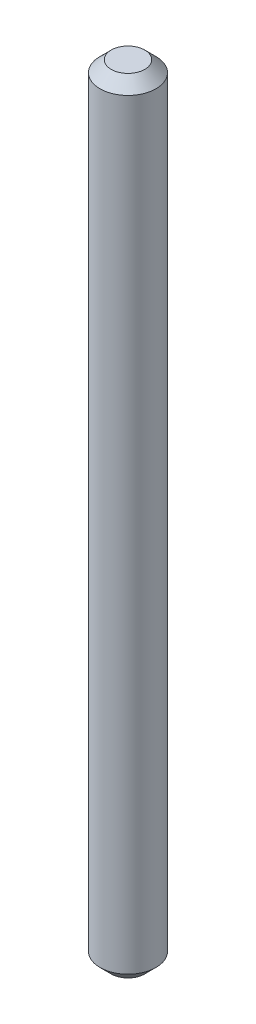
SolidWorks part; units mm, degrees
ref_plane "Plan de face" through (0, 0, 0) normal (0, 0, 1) x (1, 0, 0)
ref_plane "Plan de dessus" through (0, 0, 0) normal (0, 1, 0) x (1, 0, 0)
ref_plane "Plan de droite" through (0, 0, 0) normal (1, 0, 0) x (0, 0, -1)
sketch "Esquisse1" plane through (0, 0, 0) normal (0, 1, 0) x (1, 0, 0)
  circle A0 centre (0, 0) radius 2.5
  dimension "D1" = 5
extrude "Boss.-Extru.1" add sketch "Esquisse1" along normal blind 70
chamfer "Chanfrein1" distance 1 angle 45 2 edges at (0, 0, 2.5) (0, 70, 2.5)
